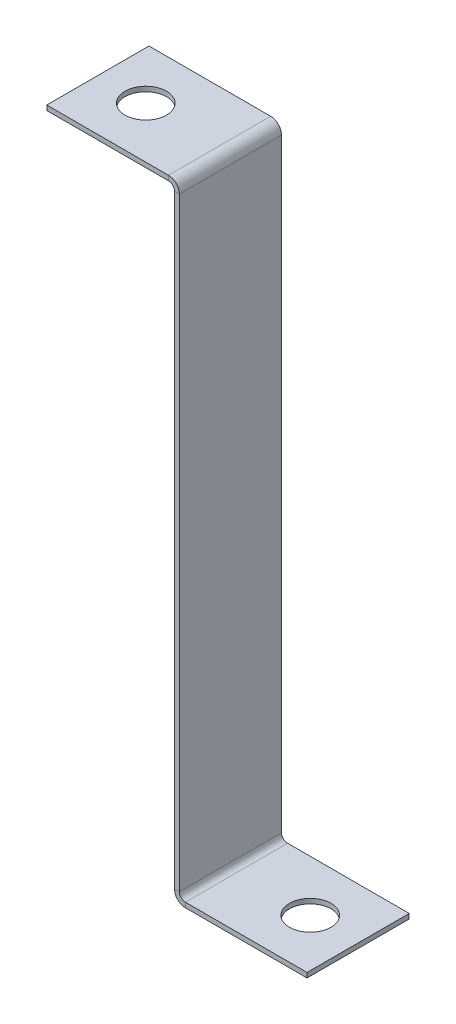
SolidWorks part; units mm, degrees
note: The reader was unsure of these and kept them because the rebuilt part matched: flange length of "Edge-Flange1", "Edge-Flange2".
material "Plain Carbon Steel"
ref_plane "Front" through (0, 0, 0) normal (0, 0, 1) x (1, 0, 0)
ref_plane "Top" through (0, 0, 0) normal (0, 1, 0) x (1, 0, 0)
ref_plane "Right" through (0, 0, 0) normal (1, 0, 0) x (0, 0, -1)
sketch "Sketch1" plane through (0, 0, 0) normal (1, 0, 0) x (0, 0, -1)
  line L0 (0, 0) -> (0, 155.575)
  line L1 (0, 0) -> (25.4, 0)
  line L2 (0, 155.575) -> (25.4, 155.575)
  line L3 (25.4, 0) -> (25.4, 155.575)
  dimension "D1" = 25.4
  dimension "D2" = 155.575
base flange "Base-Flange1" sketch "Sketch1" thickness 1.1938 reverse thickness direction no parameters "D1"=1.4986
edge flange "Edge-Flange1" sketch "Sketch10" flange angle 90 flange length 32.9438 flange position material inside bend radius 1.4986 thickness 1.1938 parameters "D6"=10
sketch "Sketch10" plane through (-1.1938, 155.575, 0) normal (0, 1, 0) x (0, 0, -1)
  line L2 (0, 0) -> (0, 31.75)
  line L3 (0, 31.75) -> (25.4, 31.75)
  line L4 (25.4, 31.75) -> (25.4, 0)
  line L7 (25.4, 0) -> (0, 0) construction
  line L8 (25.4, 0) -> (0, 0)
  dimension "D1" = 31.75
bend "EdgeBend1" bend radius 1.4986 bend angle 90 parameters "D5"=1
sketch "Sketch11" plane through (0, 155.575, 0) normal (0, 1, 0) x (1, 0, 0)
  line L0 (-2.6924, 25.4) -> (-32.9438, 25.4) construction
  line L2 (0, 25.4) -> (0, 0) construction
  circle A0 centre (-21.0376, 12.7) radius 5.1594
  dimension "D1" = 10.3187
  dimension "D2" = 12.7
  dimension "D3" = 21.0376
extrude "Cut-Extrude1" cut sketch "Sketch11" against normal through all normal cut yes
edge flange "Edge-Flange2" sketch "Sketch14" flange angle 90 flange length 32.9438 flange position material inside bend radius 1.4986 thickness 1.1938 parameters "D6"=10
sketch "Sketch14" plane through (0, 0, 0) normal (0, -1, 0) x (0, 0, -1)
  line L0 (0, 0) -> (25.4, 0) construction
  line L1 (0, 0) -> (25.4, 0)
  line L2 (0, 0) -> (0, 31.75)
  line L3 (0, 31.75) -> (25.4, 31.75)
  line L4 (25.4, 31.75) -> (25.4, 0)
  dimension "D1" = 31.75
bend "EdgeBend2" bend radius 1.4986 bend angle 90 parameters "D5"=2
sketch "Sketch15" plane through (0, 0, 0) normal (0, -1, 0) x (1, 0, 0)
  line L0 (31.75, 0) -> (1.4986, 0) construction
  line L1 (-1.1938, -25.4) -> (-1.1938, 0) construction
  circle A0 centre (19.8437, -12.7) radius 5.1594
  dimension "D1" = 10.3187
  dimension "D2" = 12.7
  dimension "D3" = 21.0376
extrude "Cut-Extrude2" cut sketch "Sketch15" against normal through all normal cut yes
sketch "Bend-Lines1" [suppressed] plane through (0, 0, 0) normal (0, 1, 0) x (1, 0, 0)
sketch "Bounding-Box1" [suppressed] plane through (0, 0, 0) normal (0, 1, 0) x (1, 0, 0)
sheet metal parameters "Sheet-Metal28" thickness 1.1938 parameters "D1"=1.4986
flat pattern "Flat-Pattern28" [suppressed]
sketch "Bend-Lines2" plane through (0, 0, 0) normal (0, 1, 0) x (1, 0, 0)
sketch3d "Bounding-Box2" [suppressed]
  line L0 (-25.4, 161.1312, 0) -> (-25.4, 0, 0) construction
  line L1 (0, 161.1312, 0) -> (0, 0, 0) construction
  line L2 (-25.4, 161.1312, 0) -> (0, 161.1312, 0) construction
  line L3 (-25.4, 0, 0) -> (0, 0, 0) construction
sheet metal parameters "Sheet-Metal29" thickness 1.1938 parameters "D1"=1.4986
flat pattern "Flat-Pattern28"
sketch "Bend-Lines2" plane through (0, 0, 0) normal (1, 0, 0) x (0, 0, -1)
  line L0 (25.4, 160.0847) -> (0, 160.0847) construction
  line L1 (25.4, 160.0847) -> (0, 160.0847) construction
sketch3d "Bounding-Box2" [suppressed]
  line L0 (25.4, 188.2481, 0) -> (25.4, 0, 0) construction
  line L1 (0, 188.2481, 0) -> (0, 0, 0) construction
  line L2 (25.4, 188.2481, 0) -> (0, 188.2481, 0) construction
  line L3 (25.4, 0, 0) -> (0, 0, 0) construction
bend of the flat pattern "Flatten-<EdgeBend1>1"
sheet metal parameters "Sheet-Metal30" thickness 1.1938 parameters "D1"=1.4986
flat pattern "Flat-Pattern28"
sketch "Bend-Lines2" plane through (0, 0, 0) normal (1, 0, 0) x (0, 0, -1)
  line L0 (25.4, 160.0847) -> (0, 160.0847) construction
  line L1 (25.4, 160.0847) -> (0, 160.0847) construction
sketch3d "Bounding-Box2" [suppressed]
  line L0 (25.4, 188.2481, 0) -> (25.4, 0, 0) construction
  line L1 (0, 188.2481, 0) -> (0, 0, 0) construction
  line L2 (25.4, 188.2481, 0) -> (0, 188.2481, 0) construction
  line L3 (25.4, 0, 0) -> (0, 0, 0) construction
bend of the flat pattern "Flatten-<EdgeBend1>1"
sheet metal parameters "Sheet-Metal31" thickness 1.1938 parameters "D1"=1.4986
flat pattern "Flat-Pattern28" [suppressed]
sketch "Bend-Lines2" plane through (0, 0, 0) normal (1, 0, 0) x (0, 0, -1)
  line L0 (25.4, 160.0847) -> (0, 160.0847) construction
  line L1 (25.4, 160.0847) -> (0, 160.0847) construction
  line L2 (0, 1.0466) -> (25.4, 1.0466) construction
  line L3 (0, 1.0466) -> (25.4, 1.0466) construction
sketch3d "Bounding-Box2" [suppressed]
  line L0 (25.4, 191.9819, 0) -> (25.4, -30.8506, 0) construction
  line L1 (0, 191.9819, 0) -> (0, -30.8506, 0) construction
  line L2 (25.4, 191.9819, 0) -> (0, 191.9819, 0) construction
  line L3 (25.4, -30.8506, 0) -> (0, -30.8506, 0) construction
bend of the flat pattern "Flatten-<EdgeBend1>1"
bend of the flat pattern "Flatten-<EdgeBend2>1"
sketch "Sketch15-1" [suppressed] plane through (-1.1938, 0.8994, 0) normal (-1, 0, 0) x (0, -1, 0)
  line L0 (31.75, 0) -> (-191.0825, 0) construction
  circle A0 centre (16.5658, -12.7) radius 5.1594
  dimension "D1" = 10.3187
  dimension "D2" = 12.7
sheet metal parameters "Sheet-Metal32" thickness 1.1938 parameters "D1"=1.4986
flat pattern "Flat-Pattern28" [suppressed]
sketch "Bend-Lines2" plane through (0, 0, 0) normal (1, 0, 0) x (0, 0, -1)
  line L0 (25.4, 154.5284) -> (0, 154.5284) construction
  line L1 (25.4, 154.5284) -> (0, 154.5284) construction
  line L2 (0, 1.0466) -> (25.4, 1.0466) construction
  line L3 (0, 1.0466) -> (25.4, 1.0466) construction
sketch3d "Bounding-Box2" [suppressed]
  line L0 (25.4, 186.4256, 0) -> (25.4, -30.8506, 0) construction
  line L1 (0, 186.4256, 0) -> (0, -30.8506, 0) construction
  line L2 (25.4, 186.4256, 0) -> (0, 186.4256, 0) construction
  line L3 (25.4, -30.8506, 0) -> (0, -30.8506, 0) construction
bend of the flat pattern "Flatten-<EdgeBend1>1"
bend of the flat pattern "Flatten-<EdgeBend2>1"
sketch "Sketch15-1" [suppressed] plane through (-1.1938, 0.8994, 0) normal (-1, 0, 0) x (0, -1, 0)
  line L0 (31.75, 0) -> (-185.5262, 0) construction
  line L1 (-1.1938, -25.4) -> (-1.1938, 0) construction
  circle A0 centre (19.8437, -12.7) radius 5.1594
  dimension "D1" = 10.3187
  dimension "D2" = 12.7
  dimension "D3" = 21.0376
equation "\"Total Cutting Length\"= \"Cutting Length-Outer\" + \"Cutting Length-Inner\""
equation "\"Amount in ft^2\"= \"Bounding Box Area-Blank\" / 144"
